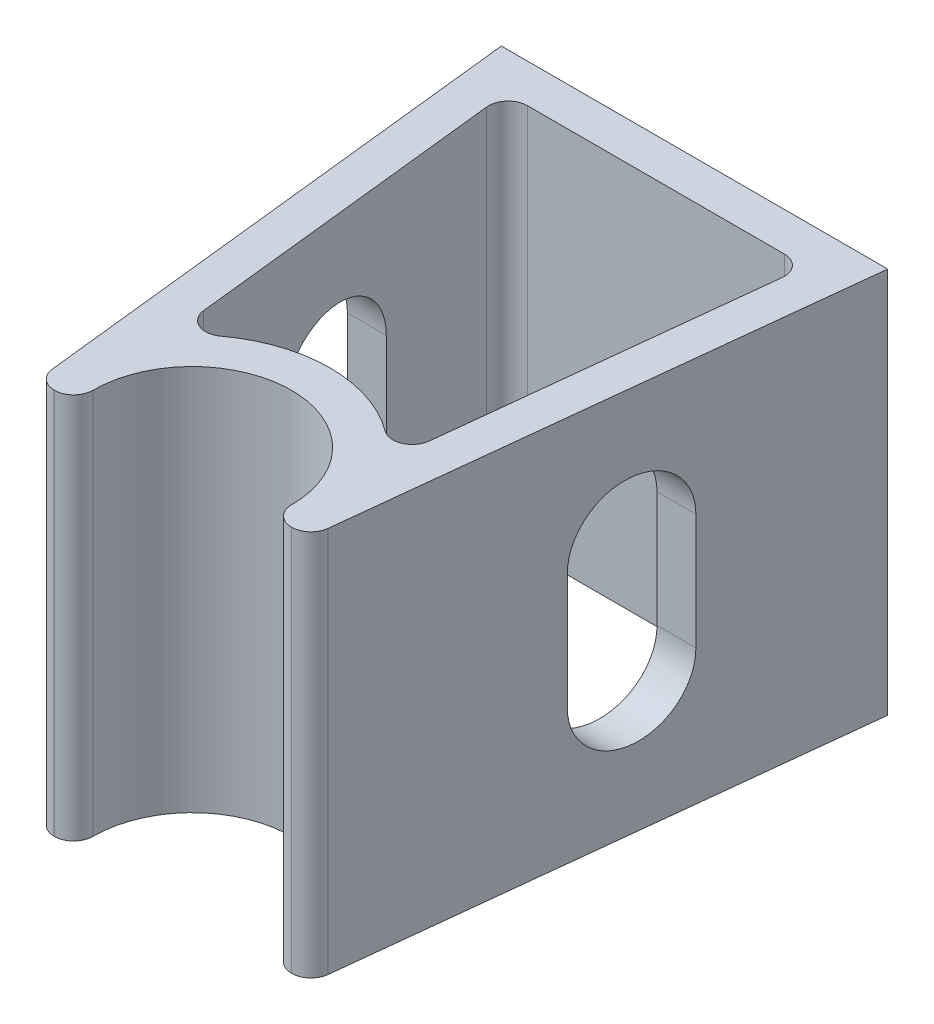
SolidWorks part; units mm, degrees
material "ABS"
ref_plane "Front Plane" through (0, 0, 0) normal (0, 0, 1) x (1, 0, 0)
ref_plane "Top Plane" through (0, 0, 0) normal (0, 1, 0) x (1, 0, 0)
ref_plane "Right Plane" through (0, 0, 0) normal (1, 0, 0) x (0, 0, -1)
sketch "Sketch1" plane through (0, 0, 0) normal (0, 1, 0) x (1, 0, 0)
  line L0 (-12.6, -2.5) -> (-17.6, -2.5)
  line L1 (-17.6, -2.5) -> (-25, 65)
  line L2 (-25, 65) -> (25, 65)
  line L3 (25, 65) -> (17.6, -2.5)
  line L4 (17.6, -2.5) -> (12.6, -2.5)
  arc A0 (12.6, -2.5) -> (-12.6, -2.5) centre (0, 0) ccw
  point P4 (0, 12.8456)
  dimension "D1" = 25.2
  dimension "D2" = 5
  dimension "D3" = 65
  dimension "D4" = 50
  dimension "D5" = 2.5
extrude "Boss-Extrude1" add sketch "Sketch1" along normal blind 50
sketch "Sketch2" plane through (0, 50, 0) normal (0, 1, 0) x (1, 0, 0)
  line L10 (14.0503, 11.0025) -> (19.4219, 60)
  line L11 (19.4219, 60) -> (-19.4219, 60)
  line L12 (-19.4219, 60) -> (-14.0503, 11.0025)
  line L13 (14.0503, 11.0025) -> (19.4219, 60)
  line L14 (19.4219, 60) -> (-19.4219, 60)
  line L15 (-19.4219, 60) -> (-14.0503, 11.0025)
  arc A2 (14.0503, 11.0025) -> (-14.0503, 11.0025) centre (0, 0) ccw
  arc A3 (14.0503, 11.0025) -> (-14.0503, 11.0025) centre (0, 0) ccw
  dimension "D1" = 5
extrude "Cut-Extrude1" cut sketch "Sketch2" against normal through all both and the other way through all
fillet "Fillet2" radius 2.5 8 edges at (-19.4219, 25, -60) (19.4219, 25, -60) (14.0503, 25, -11.0025) (-14.0503, 25, -11.0025) (17.6, 25, 2.5) (12.6, 25, 2.5) (-17.6, 25, 2.5) (-12.6, 25, 2.5)
sketch "Sketch3" plane through (0, 0, 0) normal (1, 0, 0) x (0, 0, -1)
  line L0 (35.1276, 0) -> (35.1276, 50) construction
  line L1 (-0.2724, 0) -> (65, 0) construction
  line L2 (-0.2724, 50) -> (65, 50) construction
  line L3 (35.1276, 32.5) -> (35.1276, 17.5) construction
  line L4 (42.6276, 32.5) -> (42.6276, 17.5)
  line L5 (27.6276, 32.5) -> (27.6276, 17.5)
  arc A1 (42.6276, 32.5) -> (27.6276, 32.5) centre (35.1276, 32.5) ccw
  arc A2 (27.6276, 17.5) -> (42.6276, 17.5) centre (35.1276, 17.5) ccw
  point P10 (35.1276, 25)
  dimension "D1" = 35.4
  dimension "D2" = 15
  dimension "D3" = 15
extrude "Cut-Extrude2" cut sketch "Sketch3" against normal through all both and the other way through all
